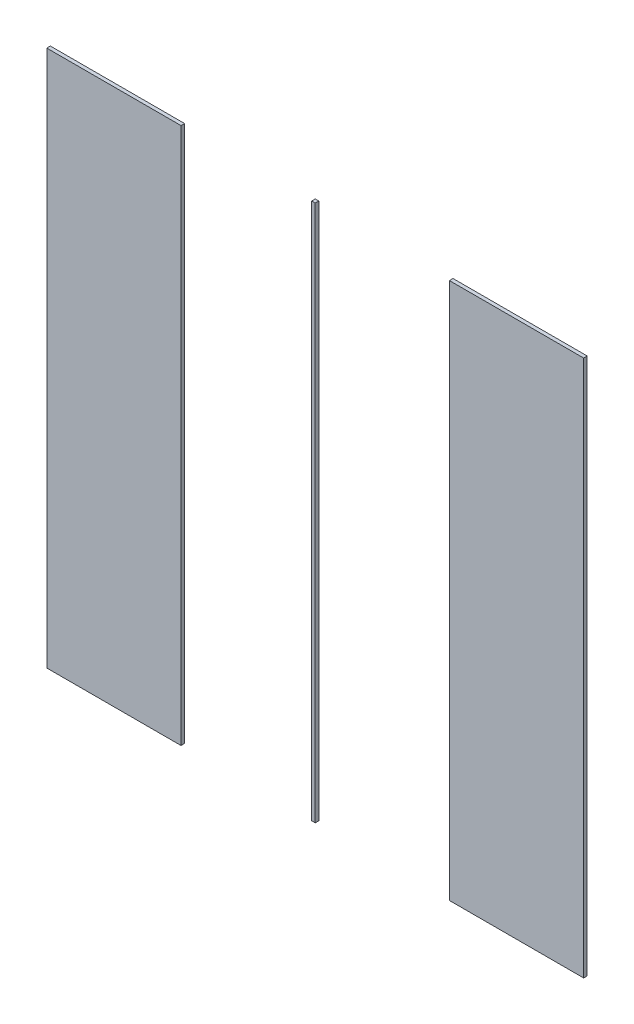
SolidWorks part; units mm, degrees
ref_plane "Front Plane" through (0, 0, 0) normal (0, 0, 1) x (1, 0, 0)
ref_plane "Top Plane" through (0, 0, 0) normal (0, 1, 0) x (1, 0, 0)
ref_plane "Right Plane" through (0, 0, 0) normal (1, 0, 0) x (0, 0, -1)
sketch "Sketch1" plane through (0, 0, 0) normal (0, 0, 1) x (1, 0, 0)
  line L1 (-375, 750) -> (375, 750)
  line L2 (-750, 750) -> (750, 750)
  line L3 (-750, 750) -> (-750, -750)
  line L4 (-750, -750) -> (750, -750)
  line L5 (750, 750) -> (750, -750)
  line L6 (-375, 750) -> (-375, -750)
  line L7 (-375, -750) -> (375, -750)
  line L8 (375, 750) -> (375, -750)
  point P0 (-750, 0)
  point P1 (0, 750)
  point P11 (0, 750)
  dimension "D1" = 1500
  dimension "D2" = 750
  dimension "D3" = 1500
extrude "Boss-Extrude2" add sketch "Sketch1" along normal blind 10 contours L6 L2 L3 L4 | L2 L8 L4 L5 region at (-562.5, 0, 0) region at (562.5, 0, 0)
sketch "Sketch4" plane through (0, 0, 0) normal (0, 0, 1) x (1, 0, 0)
  line L4 (0, 750) -> (0, -749.6267)
extrude "Extrude-Thin4" add sketch "Sketch4" along normal blind 10 separate body thin thin type one direction wall 10
equation "\"Scale\"= 8"
equation "\"Tile Size\"= \"Road Size\" * 2"
equation "\"Road Size\"= \"Real Lane Size\" * 2 / \"Scale\""
equation "\"Real Lane Size\"= 3m"
